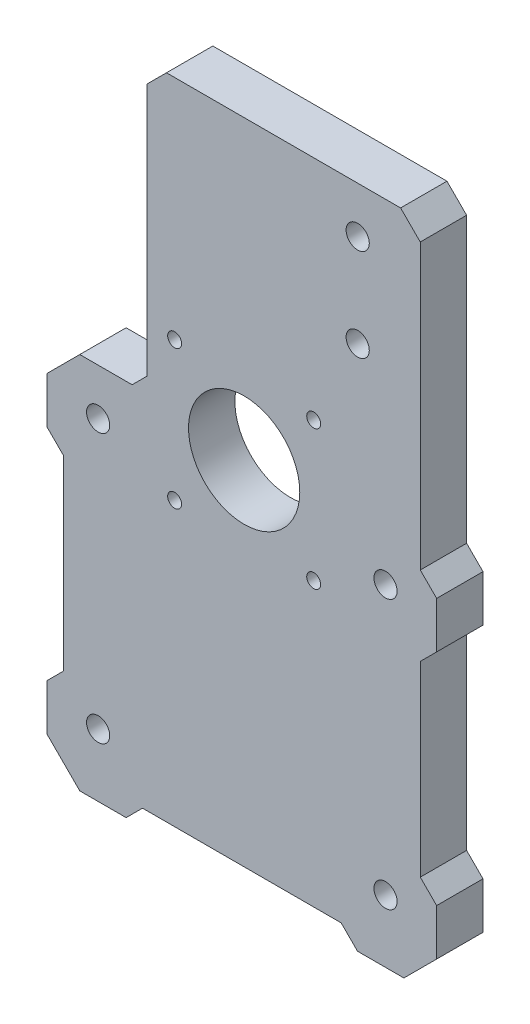
SolidWorks part; units mm, degrees
ref_plane "Alzado" through (0, 0, 0) normal (0, 0, 1) x (1, 0, 0)
ref_plane "Planta" through (0, 0, 0) normal (0, 1, 0) x (1, 0, 0)
ref_plane "Vista lateral" through (0, 0, 0) normal (1, 0, 0) x (0, 0, -1)
sketch "Croquis1" plane through (0, 0, 0) normal (0, 0, 1) x (1, 0, 0)
  line L0 (0, 0) -> (0, 36.5) construction
  line L5 (31, 29) -> (-31, 29)
  line L10 (31, 29) -> (31, -29)
  line L11 (31, -29) -> (-31, -29)
  line L12 (-31, 29) -> (-31, -29)
  line L13 (31, 29) -> (-31, -29) construction
  line L14 (31, -29) -> (-31, 29) construction
  line L15 (-38.5, 39) -> (-20.5, 39)
  line L16 (-38.5, 39) -> (-38.5, -39)
  line L17 (-38.5, -39) -> (38.5, -39)
  line L18 (38.5, 39) -> (38.5, -39)
  line L19 (-38.5, 39) -> (38.5, -39) construction
  line L20 (-38.5, -39) -> (38.5, 39) construction
  line L21 (38.5, 39) -> (38.5, 96.7574)
  line L26 (34.2574, 101) -> (-16.2574, 101)
  line L27 (-20.5, 96.7574) -> (-20.5, 39)
  line L28 (34.2574, 101) -> (38.5, 96.7574)
  line L29 (-16.2574, 101) -> (-20.5, 96.7574)
  circle A0 centre (-31, 29) radius 2.5
  circle A1 centre (31, 29) radius 2.5
  circle A2 centre (31, -29) radius 2.5
  circle A3 centre (-31, -29) radius 2.5
  point P0 (0, 0)
  point P5 (0, 0)
  dimension "D5" = 36.5
  dimension "D6" = 62
  dimension "D1" = 62
  dimension "D2" = 58
  dimension "D3" = 78
  dimension "D4" = 77
  dimension "D7" = 59
  dimension "D8" = 135
  dimension "D9" = 6
  dimension "D10" = 45
  dimension "D11" = 6
extrude "Saliente-Extruir1" add sketch "Croquis1" along normal blind 10 contours L26 L29 L27 L15 L16 L17 L18 L21 L28 A3 L12 A0 L5 A1 L10 A2 L11 | A3 L11 A2 L10 A1 L5 A0 L12 region at (0, 0, 0) region at (5.4681, 42.4409, 0)
sketch "Croquis9" plane through (0, 0, 10) normal (0, 0, 1) x (1, 0, 0)
  line L0 (21.4289, -39) -> (24.9645, -42.5355)
  line L1 (-38.5, -39) -> (38.5, -39) construction
  line L2 (24.9645, -42.5355) -> (34.9645, -42.5355)
  line L3 (34.9645, -42.5355) -> (42.0355, -35.4645)
  line L4 (42.0355, -35.4645) -> (42.0355, -25.4645)
  line L5 (42.0355, -25.4645) -> (38.5, -21.9289)
  line L6 (38.5, 96.7574) -> (38.5, -39) construction
  line L7 (0, -5.5) -> (0, 5.5) construction
  line L8 (-42.0355, -25.4645) -> (-38.5, -21.9289)
  line L9 (-42.0355, -35.4645) -> (-42.0355, -25.4645)
  line L10 (-34.9645, -42.5355) -> (-42.0355, -35.4645)
  line L11 (-24.9645, -42.5355) -> (-34.9645, -42.5355)
  line L12 (-21.4289, -39) -> (-24.9645, -42.5355)
  line L13 (-38.5, -21.9289) -> (-38.5, -30.4645)
  line L14 (-29.9645, -39) -> (-21.4289, -39)
  line L15 (-29.9645, -39) -> (-38.5, -30.4645)
  line L16 (38.5, -21.9289) -> (38.5, -30.4645)
  line L17 (29.9645, -39) -> (21.4289, -39)
  line L18 (29.9645, -39) -> (38.5, -30.4645)
  line L19 (-38.5, 39) -> (-20.5, 39) construction
  line L21 (-23.668, 39) -> (-20.1325, 42.5355)
  line L22 (-34.9645, 39) -> (-42.0355, 31.9289)
  line L23 (-42.0355, 31.9289) -> (-42.0355, 21.9289)
  line L24 (-42.0355, 21.9289) -> (-38.5, 18.3934)
  line L25 (-38.5, 39) -> (-38.5, -39) construction
  line L26 (42.0355, 21.9289) -> (38.5, 18.3934)
  line L27 (42.0355, 31.9289) -> (42.0355, 21.9289)
  line L28 (34.9645, 39) -> (42.0355, 31.9289)
  line L29 (-34.9645, 39) -> (-38.5, 18.3934)
  line L30 (38.5, 18.3934) -> (34.9645, 39)
  line M29 (-20.5, 96.7574) -> (-20.5, 39)
  line M30 (-20.5, 39) -> (-38.5, 39)
  line M31 (-38.5, 39) -> (-38.5, -39)
  line M32 (-38.5, -39) -> (38.5, -39)
  line M33 (38.5, -39) -> (38.5, 96.7574)
  dimension "D1" = 45
  dimension "D2" = 45
  dimension "D3" = 10
  dimension "D4" = 10
  dimension "D5" = 10
  dimension "D6" = 5
  dimension "D7" = 5
  dimension "D8" = 45
  dimension "D10" = 10
  dimension "D12" = 10
  dimension "D13" = 135
  dimension "D14" = 5
extrude "Saliente-Extruir2" add sketch "Croquis9" against normal through all contours L29 L22 M31 | L23 L24 L22 M31 | L30 L28 M33 | L28 L26 L27 M33 | L4 L5 L3 M33 | L2 L3 L0 M32 | L18 M32 M33 | L10 L8 L9 M31 | L15 M32 M31 | L12 L10 L11 M32 | L21 M30 M29 region at (29.9645, -40.6139, 10) region at (37.3215, 30.9526, 10) region at (40.1139, 26.9289, 10) region at (-21.556, 40.056, 10) region at (-40.1139, 26.9289, 10) region at (-37.3215, 30.9526, 10) region at (-29.9645, -40.6139, 10) region at (35.6548, -36.1548, 10) region at (40.1139, -30.4645, 10) region at (-35.6548, -36.1548, 10) region at (-40.1139, -30.4645, 10)
sketch "Croquis10" plane through (0, 0, 10) normal (0, 0, 1) x (1, 0, 0)
  line L0 (-38.5, 35.4645) -> (-34.9645, 39)
  line L1 (-38.5, 39) -> (-23.668, 39) construction
  line L2 (-34.9645, 39) -> (-38.5, 39)
  line L3 (-38.5, 39) -> (-38.5, 35.4645)
  line L4 (38.5, 91) -> (25, 91) construction
  line L5 (38.5, 96.7574) -> (38.5, 35.4645) construction
  line L6 (34.2574, 101) -> (-16.2574, 101) construction
  line L7 (-38.5, 18.3934) -> (-38.5, -21.9289) construction
  line L8 (-21.4289, -39) -> (21.4289, -39) construction
  line L10 (-14.5, 52) -> (15.5, 52)
  line L11 (-14.5, 52) -> (-14.5, 22)
  line L12 (-14.5, 22) -> (15.5, 22)
  line L13 (15.5, 52) -> (15.5, 22)
  line L14 (-14.5, 52) -> (15.5, 22) construction
  line L15 (-14.5, 22) -> (15.5, 52) construction
  circle A0 centre (25, 91) radius 2.5
  circle A2 centre (25, 71) radius 2.5
  circle A3 centre (0.5, 37) radius 12
  circle A4 centre (-14.5, 52) radius 1.5
  circle A5 centre (15.5, 52) radius 1.5
  circle A6 centre (15.5, 22) radius 1.5
  circle A7 centre (-14.5, 22) radius 1.5
  line M22 (-23.668, 39) -> (-38.5, 39)
  line M23 (-38.5, 39) -> (-38.5, 35.4645)
  dimension "D1" = 13.5
  dimension "D2" = 5
  dimension "D3" = 10
  dimension "D5" = 24
  dimension "D8" = 2
  dimension "D6" = 39
  dimension "D7" = 76
  dimension "D9" = 2
  dimension "D10" = 20
  dimension "D4" = 2
extrude "Cortar-Extruir1" cut sketch "Croquis10" against normal through all contours L0 M23 M22 | A2 | A0 | A3 | A4 | A5 | A6 | A7 region at (-37.3215, 37.8215, 10) region at (25, 91, 10) region at (25, 71, 10) region at (0.5, 37, 10)
